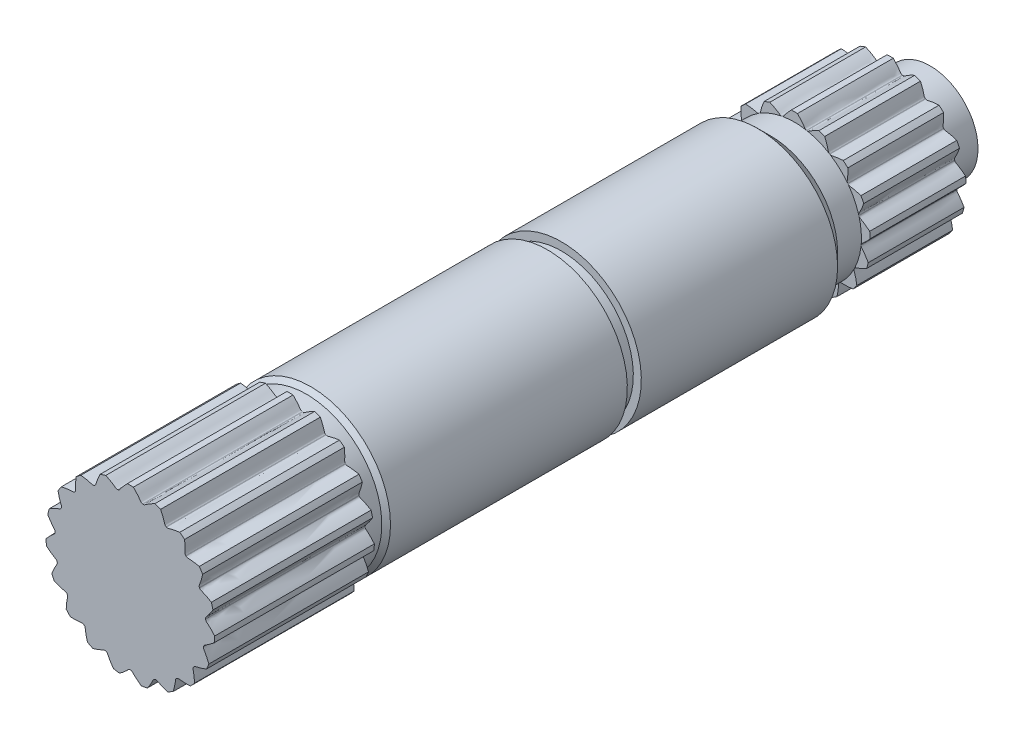
SolidWorks part; units mm, degrees
material "Alloy Steel"
ref_plane "Front Plane" through (0, 0, 0) normal (0, 0, 1) x (1, 0, 0)
ref_plane "Top Plane" through (0, 0, 0) normal (0, 1, 0) x (1, 0, 0)
ref_plane "Right Plane" through (0, 0, 0) normal (1, 0, 0) x (0, 0, -1)
sketch "Sketch12" plane through (0, 0, 0) normal (0, 0, 1) x (1, 0, 0)
  circle A0 centre (0, 0) radius 10
  dimension "D1" = 20
extrude "Shaft" add sketch "Sketch12" along normal mid plane 60
sketch "Sketch13" plane through (0, 0, 30) normal (0, 0, 1) x (1, 0, 0)
  circle A0 centre (0, 0) radius 9.4556
  dimension "D1" = 18.9113
extrude "Motor side relief" add sketch "Sketch13" along normal blind 1.587
sketch "Sketch14" plane through (0, 0, -30) normal (0, 0, -1) x (-1, 0, 0)
  circle A0 centre (0, 0) radius 8.3981
  dimension "D1" = 16.7963
extrude "Gear side relief" add sketch "Sketch14" along normal blind 1.587
sketch "Sketch15" plane through (0, 0, 31.587) normal (0, 0, 1) x (1, 0, 0)
  line L0 (5.7898, -7.4758) -> (5.8078, -7.4618)
  line L1 (5.8078, -7.4618) -> (5.8257, -7.4478)
  line L2 (7.9035, -5.1908) -> (7.9159, -5.1717)
  line L3 (7.9159, -5.1717) -> (7.9284, -5.1527)
  line L4 (9.1607, -2.3432) -> (9.1663, -2.3212)
  line L5 (9.1663, -2.3212) -> (9.1719, -2.2992)
  line L6 (9.4252, 0.7582) -> (9.4233, 0.7808)
  line L7 (9.4233, 0.7808) -> (9.4214, 0.8035)
  line L8 (8.6683, 3.7775) -> (8.6592, 3.7983)
  line L9 (8.6592, 3.7983) -> (8.6501, 3.8191)
  line L10 (6.9721, 6.3874) -> (6.9567, 6.4041)
  line L11 (6.9567, 6.4041) -> (6.9413, 6.4208)
  line L12 (4.5204, 8.3051) -> (4.5004, 8.316)
  line L13 (4.5004, 8.316) -> (4.4804, 8.3268)
  line L14 (1.5788, 9.3229) -> (1.5563, 9.3267)
  line L15 (1.5563, 9.3267) -> (1.5339, 9.3304)
  line L16 (-1.5339, 9.3304) -> (-1.5563, 9.3267)
  line L17 (-1.5563, 9.3267) -> (-1.5788, 9.3229)
  line L18 (-4.4804, 8.3268) -> (-4.5004, 8.316)
  line L19 (-4.5004, 8.316) -> (-4.5204, 8.3051)
  line L20 (-6.9413, 6.4208) -> (-6.9567, 6.4041)
  line L21 (-6.9567, 6.4041) -> (-6.9721, 6.3874)
  line L22 (-8.6501, 3.8191) -> (-8.6592, 3.7983)
  line L23 (-8.6592, 3.7983) -> (-8.6683, 3.7775)
  line L24 (-9.4214, 0.8035) -> (-9.4233, 0.7808)
  line L25 (-9.4233, 0.7808) -> (-9.4252, 0.7582)
  line L26 (-9.1719, -2.2992) -> (-9.1663, -2.3212)
  line L27 (-9.1663, -2.3212) -> (-9.1607, -2.3432)
  line L28 (-7.9284, -5.1527) -> (-7.9159, -5.1717)
  line L29 (-7.9159, -5.1717) -> (-7.9035, -5.1908)
  line L30 (-5.8257, -7.4478) -> (-5.8078, -7.4618)
  line L31 (-5.8078, -7.4618) -> (-5.7898, -7.4758)
  line L32 (-3.0917, -8.9359) -> (-3.0702, -8.9433)
  line L33 (-3.0702, -8.9433) -> (-3.0487, -8.9507)
  line L34 (-0.0227, -9.4556) -> (0, -9.4556)
  line L35 (0, -9.4556) -> (0.0227, -9.4556)
  line L36 (3.0487, -8.9507) -> (3.0702, -8.9433)
  line L37 (3.0702, -8.9433) -> (3.0917, -8.9359)
  arc A0 (4.6925, -9.4774) -> (5.3676, -9.1121) centre (0, 0) ccw
  arc A1 (7.5156, -7.4402) -> (8.0355, -6.8755) centre (0, 0) ccw
  arc A2 (9.5242, -4.5968) -> (9.8326, -3.8939) centre (0, 0) ccw
  arc A3 (10.5007, -1.2552) -> (10.5641, -0.4903) centre (0, 0) ccw
  arc A4 (10.3394, 2.2224) -> (10.1509, 2.9665) centre (0, 0) ccw
  arc A5 (9.0575, 5.4591) -> (8.6377, 6.1017) centre (0, 0) ccw
  arc A6 (6.7942, 8.1043) -> (6.1885, 8.5758) centre (0, 0) ccw
  arc A7 (3.7946, 9.8713) -> (3.0686, 10.1205) centre (0, 0) ccw
  arc A8 (0.3838, 10.5685) -> (-0.3838, 10.5685) centre (0, 0) ccw
  arc A9 (-3.0686, 10.1205) -> (-3.7946, 9.8713) centre (0, 0) ccw
  arc A10 (-6.1885, 8.5758) -> (-6.7942, 8.1043) centre (0, 0) ccw
  arc A11 (-8.6377, 6.1017) -> (-9.0575, 5.4591) centre (0, 0) ccw
  arc A12 (-10.1509, 2.9665) -> (-10.3394, 2.2224) centre (0, 0) ccw
  arc A13 (-10.5641, -0.4903) -> (-10.5007, -1.2552) centre (0, 0) ccw
  arc A14 (-9.8326, -3.8939) -> (-9.5242, -4.5968) centre (0, 0) ccw
  arc A15 (-8.0355, -6.8755) -> (-7.5156, -7.4402) centre (0, 0) ccw
  arc A16 (-5.3676, -9.1121) -> (-4.6925, -9.4774) centre (0, 0) ccw
  arc A17 (-2.1181, -10.3612) -> (-1.361, -10.4876) centre (0, 0) ccw
  arc A18 (1.361, -10.4876) -> (2.1181, -10.3612) centre (0, 0) ccw
  spline S0 degree 3 poles (3.0917, -8.9359) (3.1544, -8.9142) (3.2184, -8.911) (3.3396, -8.938) (3.397, -8.9729) (3.5767, -9.0624) (3.828, -9.1783) (4.24, -9.3384) (4.5379, -9.4334) (4.6925, -9.4774) knots 0 0 0 0 0.125 0.125 0.25 0.25 0.5 0.75 1 1 1 1
  spline S1 degree 3 poles (5.3676, -9.1121) (5.4153, -8.9586) (5.4987, -8.6572) (5.5901, -8.2247) (5.6305, -7.951) (5.6538, -7.7516) (5.656, -7.6845) (5.6997, -7.5682) (5.7374, -7.5164) (5.7898, -7.4758) knots 0 0 0 0 0.25 0.5 0.75 0.75 0.875 0.875 1 1 1 1
  spline S2 degree 3 poles (5.8257, -7.4478) (5.8779, -7.407) (5.9374, -7.3832) (6.0608, -7.3694) (6.1265, -7.3837) (6.3255, -7.41) (6.6008, -7.438) (7.0425, -7.4557) (7.3551, -7.4488) (7.5156, -7.4402) knots 0 0 0 0 0.125 0.125 0.25 0.25 0.5 0.75 1 1 1 1
  spline S3 degree 3 poles (8.0355, -6.8755) (8.0308, -6.7148) (8.0117, -6.4027) (7.9577, -5.964) (7.9071, -5.692) (7.8645, -5.4958) (7.8447, -5.4316) (7.8483, -5.3075) (7.8671, -5.2462) (7.9035, -5.1908) knots 0 0 0 0 0.25 0.5 0.75 0.75 0.875 0.875 1 1 1 1
  spline S4 degree 3 poles (7.9284, -5.1527) (7.9645, -5.0971) (8.013, -5.0552) (8.1253, -5.0021) (8.192, -4.9944) (8.3888, -4.9546) (8.6583, -4.8918) (9.0817, -4.765) (9.3752, -4.6571) (9.5242, -4.5968) knots 0 0 0 0 0.125 0.125 0.25 0.25 0.5 0.75 1 1 1 1
  spline S5 degree 3 poles (9.8326, -3.8939) (9.7759, -3.7434) (9.6566, -3.4544) (9.4631, -3.057) (9.3268, -2.8161) (9.2228, -2.6445) (9.1833, -2.5901) (9.1463, -2.4716) (9.1443, -2.4075) (9.1607, -2.3432) knots 0 0 0 0 0.25 0.5 0.75 0.75 0.875 0.875 1 1 1 1
  spline S6 degree 3 poles (9.1719, -2.2992) (9.188, -2.2349) (9.2203, -2.1795) (9.3092, -2.0928) (9.3699, -2.0638) (9.543, -1.9624) (9.7775, -1.8154) (10.1368, -1.558) (10.3793, -1.3606) (10.5007, -1.2552) knots 0 0 0 0 0.125 0.125 0.25 0.25 0.5 0.75 1 1 1 1
  spline S7 degree 3 poles (10.5641, -0.4903) (10.4617, -0.3663) (10.255, -0.1317) (9.9429, 0.1813) (9.7359, 0.3649) (9.5818, 0.4935) (9.5267, 0.532) (9.4533, 0.6322) (9.4305, 0.6921) (9.4252, 0.7582) knots 0 0 0 0 0.25 0.5 0.75 0.75 0.875 0.875 1 1 1 1
  spline S8 degree 3 poles (9.4214, 0.8035) (9.4158, 0.8695) (9.4284, 0.9324) (9.4844, 1.0433) (9.5323, 1.0904) (9.6631, 1.2426) (9.8372, 1.4577) (10.0935, 1.8179) (10.2588, 2.0833) (10.3394, 2.2224) knots 0 0 0 0 0.125 0.125 0.25 0.25 0.5 0.75 1 1 1 1
  spline S9 degree 3 poles (10.1509, 2.9665) (10.0138, 3.0504) (9.7422, 3.2052) (9.3453, 3.4) (9.0899, 3.5063) (8.9024, 3.5779) (8.8378, 3.5965) (8.7358, 3.6674) (8.6948, 3.7167) (8.6683, 3.7775) knots 0 0 0 0 0.25 0.5 0.75 0.75 0.875 0.875 1 1 1 1
  spline S10 degree 3 poles (8.6501, 3.8191) (8.6233, 3.8797) (8.6148, 3.9433) (8.6317, 4.0663) (8.6618, 4.1264) (8.7361, 4.3129) (8.8308, 4.5729) (8.9563, 4.9967) (9.0265, 5.3014) (9.0575, 5.4591) knots 0 0 0 0 0.125 0.125 0.25 0.25 0.5 0.75 1 1 1 1
  spline S11 degree 3 poles (8.6377, 6.1017) (8.4808, 6.1366) (8.1736, 6.1948) (7.735, 6.2502) (7.4588, 6.2678) (7.2583, 6.2747) (7.1911, 6.2713) (7.0717, 6.3052) (7.0169, 6.3385) (6.9721, 6.3874) knots 0 0 0 0 0.25 0.5 0.75 0.75 0.875 0.875 1 1 1 1
  spline S12 degree 3 poles (6.9413, 6.4208) (6.8963, 6.4695) (6.8676, 6.5268) (6.8437, 6.6487) (6.8526, 6.7153) (6.8624, 6.9158) (6.8676, 7.1925) (6.8486, 7.6341) (6.816, 7.9451) (6.7942, 8.1043) knots 0 0 0 0 0.125 0.125 0.25 0.25 0.5 0.75 1 1 1 1
  spline S13 degree 3 poles (6.1885, 8.5758) (6.0287, 8.5578) (5.7193, 8.5131) (5.2865, 8.4231) (5.0196, 8.3501) (4.8276, 8.2914) (4.7652, 8.2664) (4.6412, 8.2597) (4.5786, 8.2734) (4.5204, 8.3051) knots 0 0 0 0 0.25 0.5 0.75 0.75 0.875 0.875 1 1 1 1
  spline S14 degree 3 poles (4.4804, 8.3268) (4.422, 8.3582) (4.3763, 8.4031) (4.3141, 8.5106) (4.3009, 8.5765) (4.245, 8.7693) (4.1601, 9.0326) (3.9988, 9.4442) (3.8669, 9.7277) (3.7946, 9.8713) knots 0 0 0 0 0.125 0.125 0.25 0.25 0.5 0.75 1 1 1 1
  spline S15 degree 3 poles (3.0686, 10.1205) (2.9233, 10.0517) (2.6452, 9.9089) (2.2651, 9.6832) (2.0363, 9.5275) (1.8738, 9.4097) (1.8229, 9.3658) (1.7078, 9.3192) (1.6441, 9.3118) (1.5788, 9.3229) knots 0 0 0 0 0.25 0.5 0.75 0.75 0.875 0.875 1 1 1 1
  spline S16 degree 3 poles (1.5339, 9.3304) (1.4685, 9.3411) (1.4107, 9.3688) (1.3169, 9.4502) (1.283, 9.5083) (1.1676, 9.6725) (1.0018, 9.894) (0.7156, 10.2309) (0.4988, 10.4563) (0.3838, 10.5685) knots 0 0 0 0 0.125 0.125 0.25 0.25 0.5 0.75 1 1 1 1
  spline S17 degree 3 poles (-0.3838, 10.5685) (-0.4988, 10.4563) (-0.7156, 10.2309) (-1.0018, 9.894) (-1.1676, 9.6725) (-1.283, 9.5083) (-1.3169, 9.4502) (-1.4107, 9.3688) (-1.4685, 9.3411) (-1.5339, 9.3304) knots 0 0 0 0 0.25 0.5 0.75 0.75 0.875 0.875 1 1 1 1
  spline S18 degree 3 poles (-1.5788, 9.3229) (-1.6441, 9.3118) (-1.7078, 9.3192) (-1.8229, 9.3658) (-1.8738, 9.4097) (-2.0363, 9.5275) (-2.2651, 9.6832) (-2.6452, 9.9089) (-2.9233, 10.0517) (-3.0686, 10.1205) knots 0 0 0 0 0.125 0.125 0.25 0.25 0.5 0.75 1 1 1 1
  spline S19 degree 3 poles (-3.7946, 9.8713) (-3.8669, 9.7277) (-3.9988, 9.4442) (-4.1601, 9.0326) (-4.245, 8.7693) (-4.3009, 8.5765) (-4.3141, 8.5106) (-4.3763, 8.4031) (-4.422, 8.3582) (-4.4804, 8.3268) knots 0 0 0 0 0.25 0.5 0.75 0.75 0.875 0.875 1 1 1 1
  spline S20 degree 3 poles (-4.5204, 8.3051) (-4.5786, 8.2734) (-4.6412, 8.2597) (-4.7652, 8.2664) (-4.8276, 8.2914) (-5.0196, 8.3501) (-5.2865, 8.4231) (-5.7193, 8.5131) (-6.0287, 8.5578) (-6.1885, 8.5758) knots 0 0 0 0 0.125 0.125 0.25 0.25 0.5 0.75 1 1 1 1
  spline S21 degree 3 poles (-6.7942, 8.1043) (-6.816, 7.9451) (-6.8486, 7.6341) (-6.8676, 7.1925) (-6.8624, 6.9158) (-6.8526, 6.7153) (-6.8437, 6.6487) (-6.8676, 6.5268) (-6.8963, 6.4695) (-6.9413, 6.4208) knots 0 0 0 0 0.25 0.5 0.75 0.75 0.875 0.875 1 1 1 1
  spline S22 degree 3 poles (-6.9721, 6.3874) (-7.0169, 6.3385) (-7.0717, 6.3052) (-7.1911, 6.2713) (-7.2583, 6.2747) (-7.4588, 6.2678) (-7.735, 6.2502) (-8.1736, 6.1948) (-8.4808, 6.1366) (-8.6377, 6.1017) knots 0 0 0 0 0.125 0.125 0.25 0.25 0.5 0.75 1 1 1 1
  spline S23 degree 3 poles (-9.0575, 5.4591) (-9.0265, 5.3014) (-8.9563, 4.9967) (-8.8308, 4.5729) (-8.7361, 4.3129) (-8.6618, 4.1264) (-8.6317, 4.0663) (-8.6148, 3.9433) (-8.6233, 3.8797) (-8.6501, 3.8191) knots 0 0 0 0 0.25 0.5 0.75 0.75 0.875 0.875 1 1 1 1
  spline S24 degree 3 poles (-8.6683, 3.7775) (-8.6948, 3.7167) (-8.7358, 3.6674) (-8.8378, 3.5965) (-8.9024, 3.5779) (-9.0899, 3.5063) (-9.3453, 3.4) (-9.7422, 3.2052) (-10.0138, 3.0504) (-10.1509, 2.9665) knots 0 0 0 0 0.125 0.125 0.25 0.25 0.5 0.75 1 1 1 1
  spline S25 degree 3 poles (-10.3394, 2.2224) (-10.2588, 2.0833) (-10.0935, 1.8179) (-9.8372, 1.4577) (-9.6631, 1.2426) (-9.5323, 1.0904) (-9.4844, 1.0433) (-9.4284, 0.9324) (-9.4158, 0.8695) (-9.4214, 0.8035) knots 0 0 0 0 0.25 0.5 0.75 0.75 0.875 0.875 1 1 1 1
  spline S26 degree 3 poles (-9.4252, 0.7582) (-9.4305, 0.6921) (-9.4533, 0.6322) (-9.5267, 0.532) (-9.5818, 0.4935) (-9.7359, 0.3649) (-9.9429, 0.1813) (-10.255, -0.1317) (-10.4617, -0.3663) (-10.5641, -0.4903) knots 0 0 0 0 0.125 0.125 0.25 0.25 0.5 0.75 1 1 1 1
  spline S27 degree 3 poles (-10.5007, -1.2552) (-10.3793, -1.3606) (-10.1368, -1.558) (-9.7775, -1.8154) (-9.543, -1.9624) (-9.3699, -2.0638) (-9.3092, -2.0928) (-9.2203, -2.1795) (-9.188, -2.2349) (-9.1719, -2.2992) knots 0 0 0 0 0.25 0.5 0.75 0.75 0.875 0.875 1 1 1 1
  spline S28 degree 3 poles (-9.1607, -2.3432) (-9.1443, -2.4075) (-9.1463, -2.4716) (-9.1833, -2.5901) (-9.2228, -2.6445) (-9.3268, -2.8161) (-9.4631, -3.057) (-9.6566, -3.4544) (-9.7759, -3.7434) (-9.8326, -3.8939) knots 0 0 0 0 0.125 0.125 0.25 0.25 0.5 0.75 1 1 1 1
  spline S29 degree 3 poles (-9.5242, -4.5968) (-9.3752, -4.6571) (-9.0817, -4.765) (-8.6583, -4.8918) (-8.3888, -4.9546) (-8.192, -4.9944) (-8.1253, -5.0021) (-8.013, -5.0552) (-7.9645, -5.0971) (-7.9284, -5.1527) knots 0 0 0 0 0.25 0.5 0.75 0.75 0.875 0.875 1 1 1 1
  spline S30 degree 3 poles (-7.9035, -5.1908) (-7.8671, -5.2462) (-7.8483, -5.3075) (-7.8447, -5.4316) (-7.8645, -5.4958) (-7.9071, -5.692) (-7.9577, -5.964) (-8.0117, -6.4027) (-8.0308, -6.7148) (-8.0355, -6.8755) knots 0 0 0 0 0.125 0.125 0.25 0.25 0.5 0.75 1 1 1 1
  spline S31 degree 3 poles (-7.5156, -7.4402) (-7.3551, -7.4488) (-7.0425, -7.4557) (-6.6008, -7.438) (-6.3255, -7.41) (-6.1265, -7.3837) (-6.0608, -7.3694) (-5.9374, -7.3832) (-5.8779, -7.407) (-5.8257, -7.4478) knots 0 0 0 0 0.25 0.5 0.75 0.75 0.875 0.875 1 1 1 1
  spline S32 degree 3 poles (-5.7898, -7.4758) (-5.7374, -7.5164) (-5.6997, -7.5682) (-5.656, -7.6845) (-5.6538, -7.7516) (-5.6305, -7.951) (-5.5901, -8.2247) (-5.4987, -8.6572) (-5.4153, -8.9586) (-5.3676, -9.1121) knots 0 0 0 0 0.125 0.125 0.25 0.25 0.5 0.75 1 1 1 1
  spline S33 degree 3 poles (-4.6925, -9.4774) (-4.5379, -9.4334) (-4.24, -9.3384) (-3.828, -9.1783) (-3.5767, -9.0624) (-3.397, -8.9729) (-3.3396, -8.938) (-3.2184, -8.911) (-3.1544, -8.9142) (-3.0917, -8.9359) knots 0 0 0 0 0.25 0.5 0.75 0.75 0.875 0.875 1 1 1 1
  spline S34 degree 3 poles (-3.0487, -8.9507) (-2.986, -8.972) (-2.9335, -9.0088) (-2.8544, -9.1046) (-2.8306, -9.1674) (-2.7437, -9.3484) (-2.6166, -9.5942) (-2.3898, -9.9736) (-2.2131, -10.2315) (-2.1181, -10.3612) knots 0 0 0 0 0.125 0.125 0.25 0.25 0.5 0.75 1 1 1 1
  spline S35 degree 3 poles (-1.361, -10.4876) (-1.229, -10.3957) (-0.9781, -10.2091) (-0.6404, -9.9239) (-0.4404, -9.7327) (-0.2995, -9.5898) (-0.2565, -9.5381) (-0.1506, -9.4732) (-0.089, -9.4555) (-0.0227, -9.4556) knots 0 0 0 0 0.25 0.5 0.75 0.75 0.875 0.875 1 1 1 1
  spline S36 degree 3 poles (0.0227, -9.4556) (0.089, -9.4555) (0.1506, -9.4732) (0.2565, -9.5381) (0.2995, -9.5898) (0.4404, -9.7327) (0.6404, -9.9239) (0.9781, -10.2091) (1.229, -10.3957) (1.361, -10.4876) knots 0 0 0 0 0.125 0.125 0.25 0.25 0.5 0.75 1 1 1 1
  spline S37 degree 3 poles (2.1181, -10.3612) (2.2131, -10.2315) (2.3898, -9.9736) (2.6166, -9.5942) (2.7437, -9.3484) (2.8306, -9.1674) (2.8544, -9.1046) (2.9335, -9.0088) (2.986, -8.972) (3.0487, -8.9507) knots 0 0 0 0 0.25 0.5 0.75 0.75 0.875 0.875 1 1 1 1
extrude "Boss-Extrude8" add sketch "Sketch15" along normal blind 20
sketch "Sketch17" plane through (0, 0, -31.587) normal (0, 0, -1) x (-1, 0, 0)
  line L38 (4.4402, 7.1283) -> (4.4211, 7.1402)
  line L39 (4.4211, 7.1402) -> (4.4019, 7.1521)
  line L40 (1.5653, 8.251) -> (1.5432, 8.2552)
  line L41 (1.5432, 8.2552) -> (1.521, 8.2593)
  line L42 (-1.521, 8.2593) -> (-1.5432, 8.2552)
  line L43 (-1.5432, 8.2552) -> (-1.5653, 8.251)
  line L44 (-4.4019, 7.1521) -> (-4.4211, 7.1402)
  line L45 (-4.4211, 7.1402) -> (-4.4402, 7.1283)
  line L46 (-6.6882, 5.079) -> (-6.7019, 5.061)
  line L47 (-6.7019, 5.061) -> (-6.7154, 5.043)
  line L48 (-8.0713, 2.32) -> (-8.0776, 2.2983)
  line L49 (-8.0776, 2.2983) -> (-8.0837, 2.2766)
  line L50 (-8.3644, -0.7524) -> (-8.3623, -0.7749)
  line L51 (-8.3623, -0.7749) -> (-8.3602, -0.7973)
  line L52 (-7.5277, -3.7232) -> (-7.5177, -3.7434)
  line L53 (-7.5177, -3.7434) -> (-7.5076, -3.7636)
  line L54 (-5.6744, -6.1911) -> (-5.6578, -6.2063)
  line L55 (-5.6578, -6.2063) -> (-5.6411, -6.2215)
  line L56 (-3.0548, -7.8229) -> (-3.0338, -7.831)
  line L57 (-3.0338, -7.831) -> (-3.0127, -7.8392)
  line L58 (-0.0226, -8.3981) -> (0, -8.3981)
  line L59 (0, -8.3981) -> (0.0226, -8.3981)
  line L60 (3.0127, -7.8392) -> (3.0338, -7.831)
  line L61 (3.0338, -7.831) -> (3.0548, -7.8229)
  line L62 (5.6411, -6.2215) -> (5.6578, -6.2063)
  line L63 (5.6578, -6.2063) -> (5.6744, -6.1911)
  line L64 (7.5076, -3.7636) -> (7.5177, -3.7434)
  line L65 (7.5177, -3.7434) -> (7.5277, -3.7232)
  line L66 (8.3602, -0.7973) -> (8.3623, -0.7749)
  line L67 (8.3623, -0.7749) -> (8.3644, -0.7524)
  line L68 (8.0837, 2.2766) -> (8.0776, 2.2983)
  line L69 (8.0776, 2.2983) -> (8.0713, 2.32)
  line L70 (6.7154, 5.043) -> (6.7019, 5.061)
  line L71 (6.7019, 5.061) -> (6.6882, 5.079)
  arc A19 (6.6912, 6.7683) -> (6.1221, 7.2872) centre (0, 0) ccw
  arc A20 (3.7944, 8.7284) -> (3.0762, 9.0066) centre (0, 0) ccw
  arc A21 (0.3851, 9.5097) -> (-0.3851, 9.5097) centre (0, 0) ccw
  arc A22 (-3.0762, 9.0066) -> (-3.7944, 8.7284) centre (0, 0) ccw
  arc A23 (-6.1221, 7.2872) -> (-6.6912, 6.7683) centre (0, 0) ccw
  arc A24 (-8.3411, 4.5835) -> (-8.6844, 3.8941) centre (0, 0) ccw
  arc A25 (-9.4336, 1.2609) -> (-9.5047, 0.494) centre (0, 0) ccw
  arc A26 (-9.2521, -2.2321) -> (-9.0413, -2.9728) centre (0, 0) ccw
  arc A27 (-7.821, -5.4236) -> (-7.3569, -6.0382) centre (0, 0) ccw
  arc A28 (-5.3336, -7.8826) -> (-4.6788, -8.288) centre (0, 0) ccw
  arc A29 (-2.1259, -9.277) -> (-1.3689, -9.4185) centre (0, 0) ccw
  arc A30 (1.3689, -9.4185) -> (2.1259, -9.277) centre (0, 0) ccw
  arc A31 (4.6788, -8.288) -> (5.3336, -7.8826) centre (0, 0) ccw
  arc A32 (7.3569, -6.0382) -> (7.821, -5.4236) centre (0, 0) ccw
  arc A33 (9.0413, -2.9728) -> (9.2521, -2.2321) centre (0, 0) ccw
  arc A34 (9.5047, 0.494) -> (9.4336, 1.2609) centre (0, 0) ccw
  arc A35 (8.6844, 3.8941) -> (8.3411, 4.5835) centre (0, 0) ccw
  spline S0 degree 3 poles (6.6882, 5.079) (6.6486, 5.1312) (6.6257, 5.1903) (6.6128, 5.3124) (6.6277, 5.3769) (6.657, 5.5736) (6.6884, 5.8472) (6.7084, 6.2901) (6.7009, 6.6058) (6.6912, 6.7683) knots 0 0 0 0 0.125 0.125 0.25 0.25 0.5 0.75 1 1 1 1 weights 1 1 1 1 1 1 1 1 1 1
  spline S1 degree 3 poles (6.1221, 7.2872) (5.9593, 7.2818) (5.6443, 7.2602) (5.2052, 7.1994) (4.9356, 7.1428) (4.7425, 7.0956) (4.6796, 7.0748) (4.5569, 7.0763) (4.4958, 7.0937) (4.4402, 7.1283) knots 0 0 0 0 0.25 0.5 0.75 0.75 0.875 0.875 1 1 1 1 weights 1 1 1 1 1 1 1 1 1 1
  spline S2 degree 3 poles (4.4019, 7.1521) (4.3461, 7.1864) (4.3033, 7.2333) (4.2472, 7.3425) (4.2378, 7.4081) (4.194, 7.602) (4.1245, 7.8685) (3.9832, 8.2887) (3.8621, 8.5804) (3.7944, 8.7284) knots 0 0 0 0 0.125 0.125 0.25 0.25 0.5 0.75 1 1 1 1 weights 1 1 1 1 1 1 1 1 1 1
  spline S3 degree 3 poles (3.0762, 9.0066) (2.9264, 8.9428) (2.6405, 8.8089) (2.253, 8.5935) (2.022, 8.4434) (1.859, 8.3296) (1.8079, 8.2875) (1.6929, 8.2446) (1.6297, 8.2388) (1.5653, 8.251) knots 0 0 0 0 0.25 0.5 0.75 0.75 0.875 0.875 1 1 1 1 weights 1 1 1 1 1 1 1 1 1 1
  spline S4 degree 3 poles (1.521, 8.2593) (1.4566, 8.2711) (1.3997, 8.2994) (1.308, 8.3809) (1.2755, 8.4387) (1.1646, 8.6037) (1.0035, 8.8271) (0.7199, 9.1679) (0.5017, 9.3961) (0.3851, 9.5097) knots 0 0 0 0 0.125 0.125 0.25 0.25 0.5 0.75 1 1 1 1 weights 1 1 1 1 1 1 1 1 1 1
  spline S5 degree 3 poles (-0.3851, 9.5097) (-0.5017, 9.3961) (-0.7199, 9.1679) (-1.0035, 8.8271) (-1.1646, 8.6037) (-1.2755, 8.4387) (-1.308, 8.3809) (-1.3997, 8.2994) (-1.4566, 8.2711) (-1.521, 8.2593) knots 0 0 0 0 0.25 0.5 0.75 0.75 0.875 0.875 1 1 1 1 weights 1 1 1 1 1 1 1 1 1 1
  spline S6 degree 3 poles (-1.5653, 8.251) (-1.6297, 8.2388) (-1.6929, 8.2446) (-1.8079, 8.2875) (-1.859, 8.3296) (-2.022, 8.4434) (-2.253, 8.5935) (-2.6405, 8.8089) (-2.9264, 8.9428) (-3.0762, 9.0066) knots 0 0 0 0 0.125 0.125 0.25 0.25 0.5 0.75 1 1 1 1 weights 1 1 1 1 1 1 1 1 1 1
  spline S7 degree 3 poles (-3.7944, 8.7284) (-3.8621, 8.5804) (-3.9832, 8.2887) (-4.1245, 7.8685) (-4.194, 7.602) (-4.2378, 7.4081) (-4.2472, 7.3425) (-4.3033, 7.2333) (-4.3461, 7.1864) (-4.4019, 7.1521) knots 0 0 0 0 0.25 0.5 0.75 0.75 0.875 0.875 1 1 1 1 weights 1 1 1 1 1 1 1 1 1 1
  spline S8 degree 3 poles (-4.4402, 7.1283) (-4.4958, 7.0937) (-4.5569, 7.0763) (-4.6796, 7.0748) (-4.7425, 7.0956) (-4.9356, 7.1428) (-5.2052, 7.1994) (-5.6443, 7.2602) (-5.9593, 7.2818) (-6.1221, 7.2872) knots 0 0 0 0 0.125 0.125 0.25 0.25 0.5 0.75 1 1 1 1 weights 1 1 1 1 1 1 1 1 1 1
  spline S9 degree 3 poles (-6.6912, 6.7683) (-6.7009, 6.6058) (-6.7084, 6.2901) (-6.6884, 5.8472) (-6.657, 5.5736) (-6.6277, 5.3769) (-6.6128, 5.3124) (-6.6257, 5.1903) (-6.6486, 5.1312) (-6.6882, 5.079) knots 0 0 0 0 0.25 0.5 0.75 0.75 0.875 0.875 1 1 1 1 weights 1 1 1 1 1 1 1 1 1 1
  spline S10 degree 3 poles (-6.7154, 5.043) (-6.7548, 4.9906) (-6.8054, 4.9523) (-6.9193, 4.9066) (-6.9854, 4.9033) (-7.1826, 4.8775) (-7.4544, 4.8329) (-7.8859, 4.7309) (-8.1874, 4.6373) (-8.3411, 4.5835) knots 0 0 0 0 0.125 0.125 0.25 0.25 0.5 0.75 1 1 1 1 weights 1 1 1 1 1 1 1 1 1 1
  spline S11 degree 3 poles (-8.6844, 3.8941) (-8.6347, 3.7391) (-8.5277, 3.442) (-8.349, 3.0363) (-8.2209, 2.7925) (-8.1225, 2.6196) (-8.0853, 2.5648) (-8.0532, 2.4464) (-8.0533, 2.3829) (-8.0713, 2.32) knots 0 0 0 0 0.25 0.5 0.75 0.75 0.875 0.875 1 1 1 1 weights 1 1 1 1 1 1 1 1 1 1
  spline S12 degree 3 poles (-8.0837, 2.2766) (-8.1015, 2.2135) (-8.1348, 2.1595) (-8.2245, 2.0757) (-8.285, 2.0487) (-8.4596, 1.9535) (-8.6968, 1.8137) (-9.0624, 1.5628) (-9.3097, 1.3665) (-9.4336, 1.2609) knots 0 0 0 0 0.125 0.125 0.25 0.25 0.5 0.75 1 1 1 1 weights 1 1 1 1 1 1 1 1 1 1
  spline S13 degree 3 poles (-9.5047, 0.494) (-9.4023, 0.3674) (-9.1952, 0.129) (-8.882, -0.1848) (-8.6745, -0.3658) (-8.5204, -0.4915) (-8.4659, -0.5291) (-8.3931, -0.628) (-8.3702, -0.6872) (-8.3644, -0.7524) knots 0 0 0 0 0.25 0.5 0.75 0.75 0.875 0.875 1 1 1 1 weights 1 1 1 1 1 1 1 1 1 1
  spline S14 degree 3 poles (-8.3602, -0.7973) (-8.354, -0.8625) (-8.3656, -0.925) (-8.419, -1.0355) (-8.4656, -1.0825) (-8.594, -1.2344) (-8.7647, -1.4504) (-9.0149, -1.8164) (-9.1747, -2.0888) (-9.2521, -2.2321) knots 0 0 0 0 0.125 0.125 0.25 0.25 0.5 0.75 1 1 1 1 weights 1 1 1 1 1 1 1 1 1 1
  spline S15 degree 3 poles (-9.0413, -2.9728) (-8.9001, -3.0539) (-8.6209, -3.2014) (-8.2155, -3.3809) (-7.9566, -3.4747) (-7.7675, -3.5362) (-7.7031, -3.5516) (-7.5995, -3.6175) (-7.5568, -3.6645) (-7.5277, -3.7232) knots 0 0 0 0 0.25 0.5 0.75 0.75 0.875 0.875 1 1 1 1 weights 1 1 1 1 1 1 1 1 1 1
  spline S16 degree 3 poles (-7.5076, -3.7636) (-7.4783, -3.8221) (-7.4666, -3.8845) (-7.4764, -4.0068) (-7.5029, -4.0675) (-7.5678, -4.2555) (-7.6489, -4.5187) (-7.75, -4.9504) (-7.8006, -5.262) (-7.821, -5.4236) knots 0 0 0 0 0.125 0.125 0.25 0.25 0.5 0.75 1 1 1 1 weights 1 1 1 1 1 1 1 1 1 1
  spline S17 degree 3 poles (-7.3569, -6.0382) (-7.1959, -6.0628) (-6.8823, -6.0994) (-6.4394, -6.1203) (-6.1641, -6.1143) (-5.9655, -6.1033) (-5.8999, -6.0945) (-5.7795, -6.1185) (-5.7227, -6.1468) (-5.6744, -6.1911) knots 0 0 0 0 0.25 0.5 0.75 0.75 0.875 0.875 1 1 1 1 weights 1 1 1 1 1 1 1 1 1 1
  spline S18 degree 3 poles (-5.6411, -6.2215) (-5.5926, -6.2655) (-5.5591, -6.3194) (-5.5241, -6.437) (-5.5269, -6.5032) (-5.5195, -6.7019) (-5.5001, -6.9766) (-5.4384, -7.4157) (-5.373, -7.7246) (-5.3336, -7.8826) knots 0 0 0 0 0.125 0.125 0.25 0.25 0.5 0.75 1 1 1 1 weights 1 1 1 1 1 1 1 1 1 1
  spline S19 degree 3 poles (-4.6788, -8.288) (-4.5198, -8.2528) (-4.2142, -8.1737) (-3.7936, -8.0332) (-3.5391, -7.9281) (-3.3579, -7.8462) (-3.2999, -7.8142) (-3.179, -7.7931) (-3.1158, -7.799) (-3.0548, -7.8229) knots 0 0 0 0 0.25 0.5 0.75 0.75 0.875 0.875 1 1 1 1 weights 1 1 1 1 1 1 1 1 1 1
  spline S20 degree 3 poles (-3.0127, -7.8392) (-2.9516, -7.8627) (-2.9009, -7.9009) (-2.8257, -7.9979) (-2.8044, -8.0606) (-2.7257, -8.2432) (-2.6084, -8.4924) (-2.3923, -8.8795) (-2.2197, -9.1439) (-2.1259, -9.277) knots 0 0 0 0 0.125 0.125 0.25 0.25 0.5 0.75 1 1 1 1 weights 1 1 1 1 1 1 1 1 1 1
  spline S21 degree 3 poles (-1.3689, -9.4185) (-1.2333, -9.3283) (-0.9769, -9.1441) (-0.6355, -8.8612) (-0.4361, -8.6712) (-0.2968, -8.5294) (-0.2543, -8.4786) (-0.1491, -8.4153) (-0.0881, -8.3979) (-0.0226, -8.3981) knots 0 0 0 0 0.25 0.5 0.75 0.75 0.875 0.875 1 1 1 1 weights 1 1 1 1 1 1 1 1 1 1
  spline S22 degree 3 poles (0.0226, -8.3981) (0.0881, -8.3979) (0.1491, -8.4153) (0.2543, -8.4786) (0.2968, -8.5294) (0.4361, -8.6712) (0.6355, -8.8612) (0.9769, -9.1441) (1.2333, -9.3283) (1.3689, -9.4185) knots 0 0 0 0 0.125 0.125 0.25 0.25 0.5 0.75 1 1 1 1 weights 1 1 1 1 1 1 1 1 1 1
  spline S23 degree 3 poles (2.1259, -9.277) (2.2197, -9.1439) (2.3923, -8.8795) (2.6084, -8.4924) (2.7257, -8.2432) (2.8044, -8.0606) (2.8257, -7.9979) (2.9009, -7.9009) (2.9516, -7.8627) (3.0127, -7.8392) knots 0 0 0 0 0.25 0.5 0.75 0.75 0.875 0.875 1 1 1 1 weights 1 1 1 1 1 1 1 1 1 1
  spline S24 degree 3 poles (3.0548, -7.8229) (3.1158, -7.799) (3.179, -7.7931) (3.2999, -7.8142) (3.3579, -7.8462) (3.5391, -7.9281) (3.7936, -8.0332) (4.2142, -8.1737) (4.5198, -8.2528) (4.6788, -8.288) knots 0 0 0 0 0.125 0.125 0.25 0.25 0.5 0.75 1 1 1 1 weights 1 1 1 1 1 1 1 1 1 1
  spline S25 degree 3 poles (5.3336, -7.8826) (5.373, -7.7246) (5.4384, -7.4157) (5.5001, -6.9766) (5.5195, -6.7019) (5.5269, -6.5032) (5.5241, -6.437) (5.5591, -6.3194) (5.5926, -6.2655) (5.6411, -6.2215) knots 0 0 0 0 0.25 0.5 0.75 0.75 0.875 0.875 1 1 1 1 weights 1 1 1 1 1 1 1 1 1 1
  spline S26 degree 3 poles (5.6744, -6.1911) (5.7227, -6.1468) (5.7795, -6.1185) (5.8999, -6.0945) (5.9655, -6.1033) (6.1641, -6.1143) (6.4394, -6.1203) (6.8823, -6.0994) (7.1959, -6.0628) (7.3569, -6.0382) knots 0 0 0 0 0.125 0.125 0.25 0.25 0.5 0.75 1 1 1 1 weights 1 1 1 1 1 1 1 1 1 1
  spline S27 degree 3 poles (7.821, -5.4236) (7.8006, -5.262) (7.75, -4.9504) (7.6489, -4.5187) (7.5678, -4.2555) (7.5029, -4.0675) (7.4764, -4.0068) (7.4666, -3.8845) (7.4783, -3.8221) (7.5076, -3.7636) knots 0 0 0 0 0.25 0.5 0.75 0.75 0.875 0.875 1 1 1 1 weights 1 1 1 1 1 1 1 1 1 1
  spline S28 degree 3 poles (7.5277, -3.7232) (7.5568, -3.6645) (7.5995, -3.6175) (7.7031, -3.5516) (7.7675, -3.5362) (7.9566, -3.4747) (8.2155, -3.3809) (8.6209, -3.2014) (8.9001, -3.0539) (9.0413, -2.9728) knots 0 0 0 0 0.125 0.125 0.25 0.25 0.5 0.75 1 1 1 1 weights 1 1 1 1 1 1 1 1 1 1
  spline S29 degree 3 poles (9.2521, -2.2321) (9.1747, -2.0888) (9.0149, -1.8164) (8.7647, -1.4504) (8.594, -1.2344) (8.4656, -1.0825) (8.419, -1.0355) (8.3656, -0.925) (8.354, -0.8625) (8.3602, -0.7973) knots 0 0 0 0 0.25 0.5 0.75 0.75 0.875 0.875 1 1 1 1 weights 1 1 1 1 1 1 1 1 1 1
  spline S30 degree 3 poles (8.3644, -0.7524) (8.3702, -0.6872) (8.3931, -0.628) (8.4659, -0.5291) (8.5204, -0.4915) (8.6745, -0.3658) (8.882, -0.1848) (9.1952, 0.129) (9.4023, 0.3674) (9.5047, 0.494) knots 0 0 0 0 0.125 0.125 0.25 0.25 0.5 0.75 1 1 1 1 weights 1 1 1 1 1 1 1 1 1 1
  spline S31 degree 3 poles (9.4336, 1.2609) (9.3097, 1.3665) (9.0624, 1.5628) (8.6968, 1.8137) (8.4596, 1.9535) (8.285, 2.0487) (8.2245, 2.0757) (8.1348, 2.1595) (8.1015, 2.2135) (8.0837, 2.2766) knots 0 0 0 0 0.25 0.5 0.75 0.75 0.875 0.875 1 1 1 1 weights 1 1 1 1 1 1 1 1 1 1
  spline S32 degree 3 poles (8.0713, 2.32) (8.0533, 2.3829) (8.0532, 2.4464) (8.0853, 2.5648) (8.1225, 2.6196) (8.2209, 2.7925) (8.349, 3.0363) (8.5277, 3.442) (8.6347, 3.7391) (8.6844, 3.8941) knots 0 0 0 0 0.125 0.125 0.25 0.25 0.5 0.75 1 1 1 1 weights 1 1 1 1 1 1 1 1 1 1
  spline S33 degree 3 poles (8.3411, 4.5835) (8.1874, 4.6373) (7.8858, 4.731) (7.4544, 4.8329) (7.1826, 4.8775) (6.9854, 4.9033) (6.9193, 4.9066) (6.8054, 4.9523) (6.7548, 4.9906) (6.7154, 5.043) knots 0 0 0 0 0.25 0.5 0.75 0.75 0.875 0.875 1 1 1 1 weights 1 1 1 1 1 1 1 1 1 1
extrude "Sun Gear Spline" add sketch "Sketch17" along normal blind 12
sketch "Sketch20" plane through (0, 0, -43.587) normal (0, 0, -1) x (-1, 0, 0)
  circle A0 centre (0, 0) radius 8.3981
chamfer "Chamfer1" distance 3 angle 45 1 edges at (10, 0, -30)
chamfer "Chamfer3" distance 1 angle 45 1 edges at (10, 0, 30)
sketch "Sketch21" plane through (0, 0, 0) normal (1, 0, 0) x (0, 0, -1)
  line L0 (0, 0) -> (72.5071, 0) construction
  line L1 (48.587, 0) -> (48.587, 6)
  line L2 (48.587, 6) -> (44.587, 6)
  line L3 (44.587, 6) -> (44.587, 7)
  line L4 (44.587, 7) -> (43.587, 7)
  line L5 (43.587, 7) -> (43.587, 0)
  line L6 (43.587, 0) -> (48.587, 0)
  line L7 (43.587, 5.079) -> (43.587, 6.7683) construction
  point P5 (0, 0)
  dimension "D1" = 14
  dimension "D2" = 12
  dimension "D3" = 1
  dimension "D4" = 4
revolve "Revolve1" add sketch "Sketch21" angle 360 about L0
sketch "Sketch23" plane through (0, 0, -37.587) normal (-0.0059, 1, 0) x (-1, -0.0059, 0)
  line L0 (10, 36.9208) -> (9, 36.9208)
  line L1 (9, 36.9208) -> (9, 35.1708)
  line L2 (9, 35.1708) -> (10, 35.1708)
  line L3 (10, 35.1708) -> (10, 36.9208)
  line L4 (10, 10.587) -> (10, 66.587) construction
  line L5 (-13.85, 36.9208) -> (13.85, 36.9208) construction
  line L7 (0, 185.3358) -> (0, -121.609) construction
  dimension "D1" = 1.75
  dimension "D2" = 1
revolve "snap ring" cut sketch "Sketch23" angle 360 about L7
